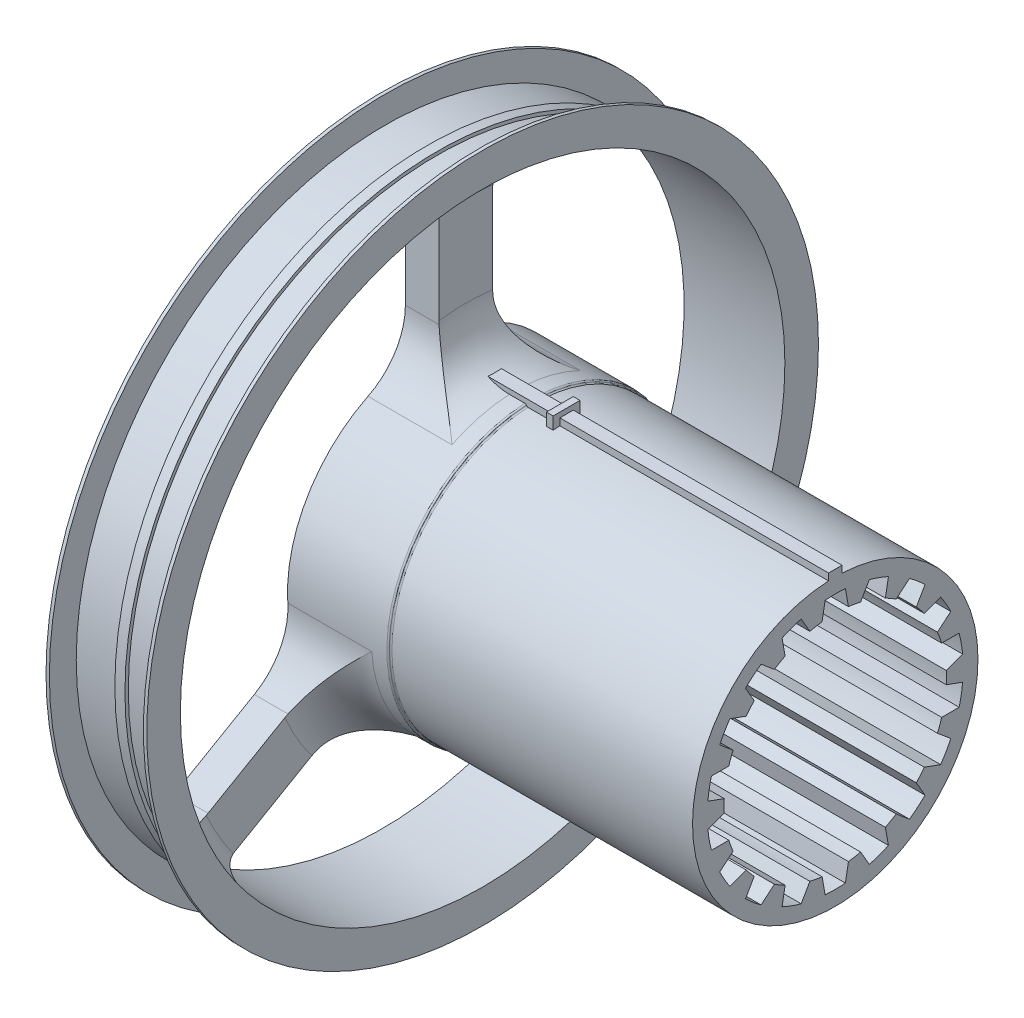
SolidWorks part; units mm, degrees
ref_plane "Płaszczyzna przednia" through (0, 0, 0) normal (0, 0, 1) x (1, 0, 0)
ref_plane "Płaszczyzna górna" through (0, 0, 0) normal (0, 1, 0) x (1, 0, 0)
ref_plane "Płaszczyzna prawa" through (0, 0, 0) normal (1, 0, 0) x (0, 0, -1)
sketch "Szkic1" plane through (0, 0, 0) normal (1, 0, 0) x (0, 0, -1)
  line L0 (14.9273, 29.543) -> (15.8289, 34.6563)
  line L1 (3.9228, 32.8667) -> (3.0212, 37.98)
  line L2 (-3.9228, 32.8667) -> (-3.0212, 37.98)
  line L3 (7.5549, 32.2263) -> (10.151, 36.7228)
  line L4 (24.1313, 22.6559) -> (26.7274, 27.1524)
  line L5 (18.1213, 27.6989) -> (22.0988, 31.0364)
  line L6 (30.4248, 13.0361) -> (34.4022, 16.3736)
  line L7 (26.502, 19.8306) -> (31.3811, 21.6064)
  line L8 (33.0486, 1.8441) -> (37.9276, 3.6199)
  line L9 (31.6862, 9.5704) -> (36.8784, 9.5704)
  line L10 (31.6862, -9.5704) -> (36.8784, -9.5704)
  line L11 (33.0486, -1.8441) -> (37.9276, -3.6199)
  line L12 (26.502, -19.8306) -> (31.3811, -21.6064)
  line L13 (30.4248, -13.0361) -> (34.4022, -16.3736)
  line L14 (18.1213, -27.6989) -> (22.0988, -31.0364)
  line L15 (24.1313, -22.6559) -> (26.7274, -27.1524)
  line L16 (7.5549, -32.2263) -> (10.151, -36.7228)
  line L17 (14.9273, -29.543) -> (15.8289, -34.6563)
  line L18 (-3.9228, -32.8667) -> (-3.0212, -37.98)
  line L19 (3.9228, -32.8667) -> (3.0212, -37.98)
  line L20 (-14.9273, -29.543) -> (-15.8289, -34.6563)
  line L21 (-7.5549, -32.2263) -> (-10.151, -36.7228)
  line L22 (-24.1313, -22.6559) -> (-26.7274, -27.1524)
  line L23 (-18.1213, -27.6989) -> (-22.0988, -31.0364)
  line L24 (-30.4248, -13.0361) -> (-34.4022, -16.3736)
  line L25 (-26.502, -19.8306) -> (-31.3811, -21.6064)
  line L26 (-33.0486, -1.8441) -> (-37.9276, -3.6199)
  line L27 (-31.6862, -9.5704) -> (-36.8784, -9.5704)
  line L28 (-31.6862, 9.5704) -> (-36.8784, 9.5704)
  line L29 (-33.0486, 1.8441) -> (-37.9276, 3.6199)
  line L30 (-26.502, 19.8306) -> (-31.3811, 21.6064)
  line L31 (-30.4248, 13.0361) -> (-34.4022, 16.3736)
  line L32 (-18.1213, 27.6989) -> (-22.0988, 31.0364)
  line L33 (-24.1313, 22.6559) -> (-26.7274, 27.1524)
  line L34 (-7.5549, 32.2263) -> (-10.151, 36.7228)
  line L35 (-14.9273, 29.543) -> (-15.8289, 34.6563)
  arc A0 (-10.151, 36.7228) -> (-15.8289, 34.6563) centre (0, 0) ccw
  arc A1 (-3.9228, 32.8667) -> (-7.5549, 32.2263) centre (0, 0) ccw
  circle A2 centre (0, 0) radius 43.1
  arc A3 (-14.9273, 29.543) -> (-18.1213, 27.6989) centre (0, 0) ccw
  arc A4 (-24.1313, 22.6559) -> (-26.502, 19.8306) centre (0, 0) ccw
  arc A5 (-30.4248, 13.0361) -> (-31.6862, 9.5704) centre (0, 0) ccw
  arc A6 (-33.0486, 1.8441) -> (-33.0486, -1.8441) centre (0, 0) ccw
  arc A7 (-31.6862, -9.5704) -> (-30.4248, -13.0361) centre (0, 0) ccw
  arc A8 (-26.502, -19.8306) -> (-24.1313, -22.6559) centre (0, 0) ccw
  arc A9 (-18.1213, -27.6989) -> (-14.9273, -29.543) centre (0, 0) ccw
  arc A10 (-7.5549, -32.2263) -> (-3.9228, -32.8667) centre (0, 0) ccw
  arc A11 (3.9228, -32.8667) -> (7.5549, -32.2263) centre (0, 0) ccw
  arc A12 (14.9273, -29.543) -> (18.1213, -27.6989) centre (0, 0) ccw
  arc A13 (24.1313, -22.6559) -> (26.502, -19.8306) centre (0, 0) ccw
  arc A14 (30.4248, -13.0361) -> (31.6862, -9.5704) centre (0, 0) ccw
  arc A15 (33.0486, -1.8441) -> (33.0486, 1.8441) centre (0, 0) ccw
  arc A16 (26.502, 19.8306) -> (24.1313, 22.6559) centre (0, 0) ccw
  arc A17 (18.1213, 27.6989) -> (14.9273, 29.543) centre (0, 0) ccw
  arc A18 (7.5549, 32.2263) -> (3.9228, 32.8667) centre (0, 0) ccw
  arc A19 (-22.0988, 31.0364) -> (-26.7274, 27.1524) centre (0, 0) ccw
  arc A20 (-31.3811, 21.6064) -> (-34.4022, 16.3736) centre (0, 0) ccw
  arc A21 (-36.8784, 9.5704) -> (-37.9276, 3.6199) centre (0, 0) ccw
  arc A22 (-37.9276, -3.6199) -> (-36.8784, -9.5704) centre (0, 0) ccw
  arc A23 (-34.4022, -16.3736) -> (-31.3811, -21.6064) centre (0, 0) ccw
  arc A24 (-26.7274, -27.1524) -> (-22.0988, -31.0364) centre (0, 0) ccw
  arc A25 (-15.8289, -34.6563) -> (-10.151, -36.7228) centre (0, 0) ccw
  arc A26 (-3.0212, -37.98) -> (3.0212, -37.98) centre (0, 0) ccw
  arc A27 (10.151, -36.7228) -> (15.8289, -34.6563) centre (0, 0) ccw
  arc A28 (22.0988, -31.0364) -> (26.7274, -27.1524) centre (0, 0) ccw
  arc A29 (31.3811, -21.6064) -> (34.4022, -16.3736) centre (0, 0) ccw
  arc A30 (3.0212, 37.98) -> (-3.0212, 37.98) centre (0, 0) ccw
  arc A31 (15.8289, 34.6563) -> (10.151, 36.7228) centre (0, 0) ccw
  arc A32 (26.7274, 27.1524) -> (22.0988, 31.0364) centre (0, 0) ccw
  arc A33 (34.4022, 16.3736) -> (31.3811, 21.6064) centre (0, 0) ccw
  arc A34 (31.6862, 9.5704) -> (30.4248, 13.0361) centre (0, 0) ccw
  arc A35 (37.9276, 3.6199) -> (36.8784, 9.5704) centre (0, 0) ccw
  arc A36 (36.8784, -9.5704) -> (37.9276, -3.6199) centre (0, 0) ccw
  point P80 (0, 0)
  dimension "D1" = 66.2
  dimension "D2" = 76.2
  dimension "D3" = 86.2
  dimension "D4" = 18
extrude "Dodanie-wyciągnięcie1" add sketch "Szkic1" along normal blind 120
sketch "Szkic2" plane through (0, 0, 0) normal (-1, 0, 0) x (0, 0, 1)
  line L0 (40.6771, -14.2473) -> (81.6338, -37.8937)
  line L1 (-8, 42.351) -> (-8, 89.6437)
  line L2 (8, 42.351) -> (8, 89.6437)
  line L3 (32.6771, -28.1037) -> (73.6338, -51.7501)
  line L4 (-32.6771, -28.1037) -> (-73.6338, -51.7501)
  line L5 (-40.6771, -14.2473) -> (-81.6338, -37.8937)
  arc A1 (-40.6771, -14.2473) -> (-32.6771, -28.1037) centre (0, 0) ccw
  arc A2 (-81.6338, -37.8937) -> (-73.6338, -51.7501) centre (0, 0) ccw
  arc A3 (8, 89.6437) -> (-8, 89.6437) centre (0, 0) ccw
  arc A4 (73.6338, -51.7501) -> (81.6338, -37.8937) centre (0, 0) ccw
  arc A5 (8, 42.351) -> (-8, 42.351) centre (0, 0) ccw
  arc A6 (32.6771, -28.1037) -> (40.6771, -14.2473) centre (0, 0) ccw
  point P20 (0, 0)
  dimension "D3" = 180
  dimension "D4" = 86.2
  dimension "D1" = 16
  dimension "D2" = 3
extrude "Dodanie-wyciągnięcie2" add sketch "Szkic2" against normal blind 10
sketch "Szkic3" plane through (0, 0, 0) normal (-1, 0, 0) x (0, 0, 1)
  circle A0 centre (0, 0) radius 90
  circle A1 centre (0, 0) radius 92
  dimension "D1" = 180
  dimension "D2" = 184
extrude "Dodanie-wyciągnięcie3" add sketch "Szkic3" against normal mid plane 30
fillet "Zaokrąglenie1" radius 20 6 edges at (5, 42.351, -8) (5, -14.2473, -40.6771) (5, -28.1037, -32.6771) (5, -28.1037, 32.6771) (5, -14.2473, 40.6771) (5, 42.351, 8)
fillet "Zaokrąglenie2" radius 15 3 edges at (10, 43.1, 0) (10, -21.55, -37.3257) (10, -21.55, 37.3257)
fillet "Zaokrąglenie3" radius 5 12 edges at (5, 89.6437, -8) (0, 90, 0) (10, 90, 0) (5, 89.6437, 8) (0, -45, -77.9423) (5, -51.7501, -73.6338) (10, -45, -77.9423) (5, -37.8937, -81.6338) (5, -37.8937, 81.6338) (0, -45, 77.9423) (10, -45, 77.9423) (5, -51.7501, 73.6338)
sketch "Szkic5" plane through (-15, 0, 0) normal (-1, 0, 0) x (0, 0, 1)
  circle A0 centre (0, 0) radius 92
  circle A1 centre (0, 0) radius 100
  dimension "D1" = 200
extrude "Dodanie-wyciągnięcie5" add sketch "Szkic5" against normal blind 1
sketch "Szkic7" plane through (15, 0, 0) normal (1, 0, 0) x (0, 0, -1)
  circle A0 centre (0, 0) radius 92
  circle A1 centre (0, 0) radius 100
extrude "Dodanie-wyciągnięcie6" add sketch "Szkic7" against normal blind 1
sketch "Szkic8" plane through (15, 0, 0) normal (1, 0, 0) x (0, 0, -1)
  circle A0 centre (0, 0) radius 92
  circle A1 centre (0, 0) radius 93
  dimension "D1" = 184
  dimension "D2" = 186
extrude "Dodanie-wyciągnięcie7" add sketch "Szkic8" along normal mid plane 3 from offset 15 offset against normal yes
sketch "Szkic9" plane through (120, 0, 0) normal (1, 0, 0) x (0, 0, -1)
  circle A0 centre (0, 0) radius 42.5
  circle A1 centre (0, 0) radius 43.1
  dimension "D1" = 85
extrude "Wytnij-wyciągnięcie1" cut sketch "Szkic9" against normal blind 90
fillet "Zaokrąglenie4" radius 0.5 1 edges at (30, 0, -42.5)
fillet "Zaokrąglenie5" radius 0.5 1 edges at (30, 0, -43.1)
sketch "Szkic10" plane through (120, 0, 0) normal (1, 0, 0) x (0, 0, -1)
  line L1 (-2, 44.5) -> (2, 44.5)
  line L2 (-2, 44.5) -> (-2, 42.4529)
  line L3 (2, 44.5) -> (2, 42.4529)
  arc A0 (2, 42.4529) -> (-2, 42.4529) centre (0, 0) ccw
extrude "Dodanie-wyciągnięcie8" add sketch "Szkic10" against normal blind 110
sketch "Szkic11" plane through (120, 0, 0) normal (1, 0, 0) x (0, 0, -1)
  line L1 (0, 46) -> (4, 46)
  line L2 (0, 46) -> (-4, 46)
  line L3 (-4, 46) -> (-4, 42.3113)
  line L4 (4, 46) -> (4, 42.3113)
  line L5 (2, 44.5) -> (-2, 44.5) construction
  arc A0 (4, 42.3113) -> (-4, 42.3113) centre (0, 0) ccw
  dimension "D3" = 1.5
extrude "Dodanie-wyciągnięcie9" add sketch "Szkic11" against normal blind 2 from offset 80 offset against normal yes
